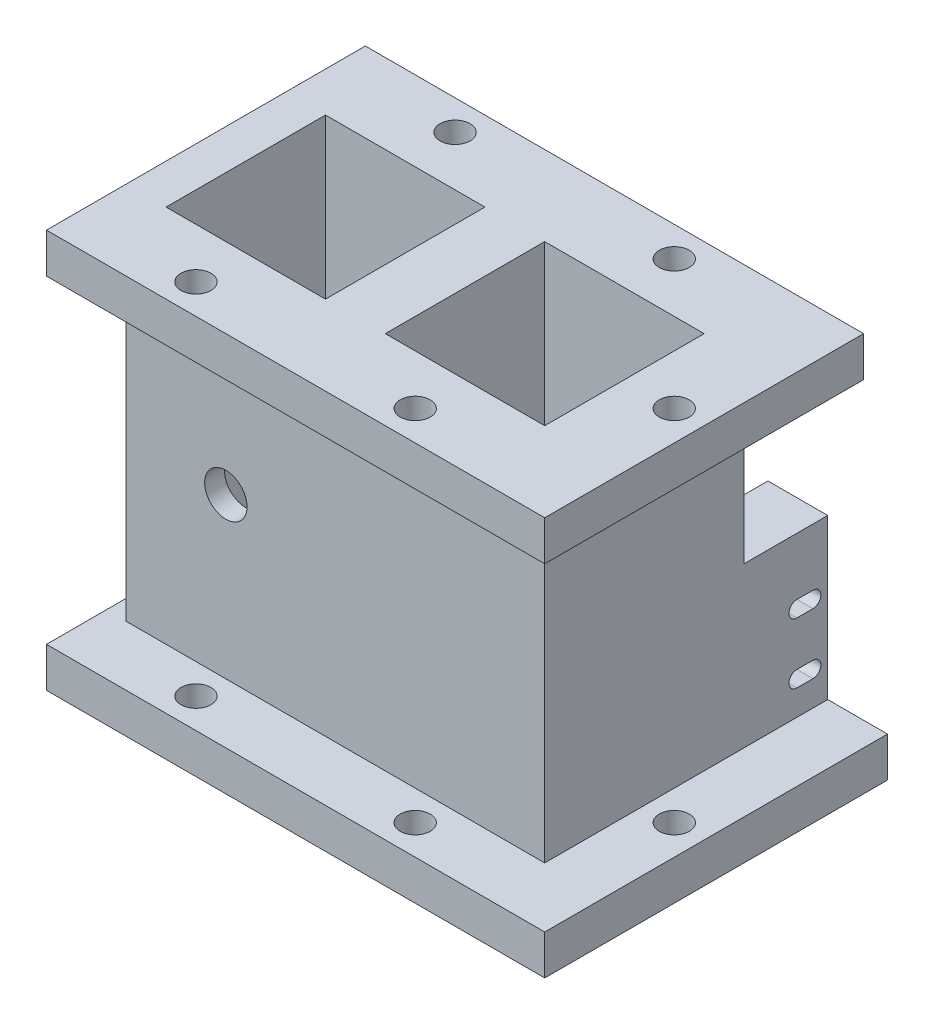
SolidWorks part; units mm, degrees
other "Markup1"
sketch "Sketch8" plane through (39.6875, 63.5, -25.4) normal (0.2237, 0.8347, -0.5032) x (-0.5017, -0.344, -0.7937)
other "Markup2"
sketch "Sketch16" plane through (-39.6875, 63.5, -25.4) normal (-0.7477, 0.2937, -0.5956) x (-0.6485, -0.1298, 0.7501)
other "Markup3"
sketch "Sketch18" plane through (40.5016, 64.1281, -25.9101) normal (0.6007, 0.1438, -0.7864) x (-0.7857, -0.0757, -0.614)
material "PPS"
ref_plane "Front Plane" through (0, 0, 0) normal (0, 0, 1) x (1, 0, 0)
ref_plane "Top Plane" through (0, 0, 0) normal (0, 1, 0) x (1, 0, 0)
ref_plane "Right Plane" through (0, 0, 0) normal (1, 0, 0) x (0, 0, -1)
sketch "Sketch2" plane through (0, 0, 0) normal (0, 1, 0) x (1, 0, 0)
  line L1 (-39.6875, -25.4) -> (39.6875, -25.4)
  line L2 (-39.6875, -25.4) -> (-39.6875, 25.4)
  line L3 (-39.6875, 25.4) -> (39.6875, 25.4)
  line L4 (39.6875, -25.4) -> (39.6875, 25.4)
  line L5 (-39.6875, -25.4) -> (39.6875, 25.4) construction
  line L6 (-39.6875, 25.4) -> (39.6875, -25.4) construction
  point P0 (0, 0)
  dimension "D1" = 50.8
  dimension "D2" = 79.375
extrude "Boss-Extrude1" add sketch "Sketch2" along normal blind 6.35 contours L4 L3 L2 L1
sketch "Sketch3" plane through (0, 6.35, 0) normal (0, 1, 0) x (1, 0, 0)
  line L0 (-39.6875, -25.4) -> (-39.6875, 25.4) construction
  line L1 (-33.3375, -12.7) -> (-7.9375, -12.7)
  line L2 (-33.3375, -12.7) -> (-33.3375, 12.7)
  line L3 (-33.3375, 12.7) -> (-7.9375, 12.7)
  line L4 (-7.9375, -12.7) -> (-7.9375, 12.7)
  line L5 (-33.3375, -12.7) -> (-7.9375, 12.7) construction
  line L6 (-33.3375, 12.7) -> (-7.9375, -12.7) construction
  line L7 (-39.6875, 0) -> (39.6875, 0) construction
  line L8 (1.5875, 12.7) -> (26.9875, 12.7)
  line L9 (1.5875, 12.7) -> (1.5875, -12.7)
  line L10 (1.5875, -12.7) -> (26.9875, -12.7)
  line L11 (26.9875, 12.7) -> (26.9875, -12.7)
  line L12 (1.5875, 12.7) -> (26.9875, -12.7) construction
  line L13 (1.5875, -12.7) -> (26.9875, 12.7) construction
  line L14 (39.6875, -25.4) -> (39.6875, 25.4) construction
  line L16 (-36.5125, -15.875) -> (30.1625, -15.875)
  line L17 (-36.5125, -15.875) -> (-36.5125, 15.875)
  line L18 (-36.5125, 15.875) -> (30.1625, 15.875)
  line L19 (30.1625, -15.875) -> (30.1625, 15.875)
  point P0 (-20.6375, 0)
  point P7 (14.2875, 0)
  dimension "D1" = 25.4
  dimension "D2" = 25.4
  dimension "D3" = 6.35
  dimension "D4" = 25.4
  dimension "D5" = 25.4
  dimension "D6" = 12.7
  dimension "D7" = 3.175
  dimension "D8" = 3.175
  dimension "D9" = 3.175
  dimension "D10" = 3.175
extrude "Boss-Extrude3" add sketch "Sketch3" along normal blind 50.8
sketch "Sketch4" plane through (0, 57.15, 0) normal (0, 1, 0) x (1, 0, 0)
  line L1 (-33.3375, 12.7) -> (-7.9375, 12.7)
  line L2 (-33.3375, 12.7) -> (-33.3375, -12.7)
  line L3 (-33.3375, -12.7) -> (-7.9375, -12.7)
  line L4 (-7.9375, 12.7) -> (-7.9375, -12.7)
  line L5 (1.5875, 12.7) -> (26.9875, 12.7)
  line L6 (1.5875, 12.7) -> (1.5875, -12.7)
  line L7 (1.5875, -12.7) -> (26.9875, -12.7)
  line L8 (26.9875, 12.7) -> (26.9875, -12.7)
ref_plane "Plane1" through (0, 31.75, 0) normal (0, 1, 0) x (1, 0, 0)
mirror "Mirror1" about plane through (0, 31.75, 0) normal (0, 1, 0) of "Boss-Extrude1"
extrude "Cut-Extrude4" cut sketch "Sketch4" against normal through all both and the other way through all
sketch "Sketch5" plane through (0, 0, 15.875) normal (0, 0, 1) x (1, 0, 0)
  line L0 (-36.5125, 31.75) -> (30.1625, 31.75) construction
  line L1 (-33.3375, 44.8114) -> (-7.9375, 44.8114) construction
  line L3 (-36.5125, 57.15) -> (-36.5125, 6.35) construction
  line L4 (30.1625, 57.15) -> (30.1625, 6.35) construction
  line L5 (-33.3375, 57.15) -> (-33.3375, 6.35) construction
  line L6 (-36.5125, 57.15) -> (30.1625, 57.15) construction
  line L7 (-36.5125, 6.35) -> (30.1625, 6.35) construction
  line L8 (-7.9375, 57.15) -> (-7.9375, 6.35) construction
  circle A0 centre (-20.6375, 31.75) radius 3.3782
  dimension "D1" = 6.7564
  dimension "D2" = 3.175
  dimension "D3" = 25.4
  dimension "D4" = 12.7
extrude "Cut-Extrude5" cut sketch "Sketch5" against normal through all
sketch "Sketch6" plane through (0, 6.35, 0) normal (0, 1, 0) x (1, 0, 0)
  line L0 (30.1625, 0) -> (39.6875, 0) construction
  line L1 (30.1625, -15.875) -> (30.1625, 15.875) construction
  line L2 (39.6875, -25.4) -> (39.6875, 25.4) construction
  circle A0 centre (34.925, 0) radius 2.3876
  dimension "D1" = 4.7752
ref_plane "Plane2" through (14.2875, 0, 0) normal (1, 0, 0) x (0, 0, -1)
ref_plane "Plane3" through (0, 0, 0) normal (0, 0, 1) x (1, 0, 0)
ref_axis "Axis1" through (14.2875, -3.175, 0) along (0, 1, 0)
extrude "Cut-Extrude6" cut sketch "Sketch6" against normal through all both and the other way through all
pattern_circular "CirPattern1" count 4 over 360 about axis through (14.2875, -3.175, 0) along (0, 1, 0) skipping 2 of "Cut-Extrude6"
sketch "Sketch7" plane through (0, 6.35, 0) normal (0, 1, 0) x (1, 0, 0)
  line L0 (-33.3375, -17.2263) -> (-33.3375, -22.8133) construction
  line L5 (-39.6875, -25.4) -> (-39.6875, 25.4) construction
  line L6 (-7.9375, -17.2263) -> (-7.9375, -22.8133) construction
  line L7 (-7.9375, -20.6375) -> (-33.3375, -20.6375) construction
  circle A1 centre (-20.6375, -20.6375) radius 2.3876
  dimension "D3" = 4.7752
  dimension "D1" = 6.35
  dimension "D2" = 25.4
extrude "Cut-Extrude7" cut sketch "Sketch7" against normal through all both and the other way through all
mirror "Mirror2" about plane through (0, 0, 0) normal (0, 0, 1) of "Cut-Extrude7"
sketch "Sketch9" plane through (0, 0, -15.875) normal (0, 0, -1) x (-1, 0, 0)
  line L0 (-30.1625, 57.15) -> (-30.1625, 6.35) construction
  line L1 (-23.8125, 6.35) -> (-1.5875, 6.35)
  line L2 (-23.8125, 6.35) -> (-23.8125, 31.75)
  line L3 (-23.8125, 31.75) -> (-1.5875, 31.75)
  line L4 (-1.5875, 6.35) -> (-1.5875, 31.75)
  line L6 (-30.1625, 6.35) -> (36.5125, 6.35) construction
  dimension "D1" = 6.35
  dimension "D2" = 28.575
  dimension "D3" = 0
  dimension "D4" = 25.4
extrude "Cut-Extrude8" cut sketch "Sketch9" against normal up to next
ref_plane "Plane5" through (30.1625, 0, 0) normal (1, 0, 0) x (0, 0, -1)
sketch "Sketch12" plane through (30.1625, 0, 0) normal (1, 0, 0) x (0, 0, -1)
  line L0 (25.4, 6.35) -> (25.4, 0) construction
  line L1 (12.7, 6.35) -> (25.4, 6.35)
  line L2 (12.7, 6.35) -> (12.7, 31.75)
  line L3 (12.7, 31.75) -> (25.4, 31.75)
  line L4 (25.4, 6.35) -> (25.4, 31.75)
  line L5 (12.7, 63.5) -> (12.7, 0) construction
  dimension "D1" = 25.4
extrude "Boss-Extrude5" add sketch "Sketch12" against normal blind 9.525
sketch "Sketch14" plane through (20.6375, 0, 0) normal (-1, 0, 0) x (0, 0, 1)
  line L0 (-12.7, 6.35) -> (-25.4, 6.35) construction
  line L1 (-25.4, 6.35) -> (-12.7, 6.35)
  line L2 (-25.4, 6.35) -> (-25.4, 26.162)
  line L3 (-25.4, 26.162) -> (-12.7, 26.162)
  line L4 (-12.7, 6.35) -> (-12.7, 26.162)
  dimension "D1" = 12.7
  dimension "D3" = 19.812
extrude "Cut-Extrude9" cut sketch "Sketch14" against normal blind 6.35
sketch "Sketch17" plane through (26.9875, 0, 0) normal (-1, 0, 0) x (0, 0, 1)
  line L8 (-12.7, 31.75) -> (-12.7, 26.162) construction
  circle A1 centre (-12.7, 26.1233) radius 5.588
  dimension "D2" = 11.176
  dimension "D1" = 0
extrude "Cut-Extrude11" cut sketch "Sketch17" along normal blind 6.985
ref_plane "Plane6" through (-50.8, 0, 0) normal (1, 0, 0) x (0, 0, -1)
sketch "Sketch19" plane through (0, 0, -25.4) normal (0, 0, -1) x (-1, 0, 0)
  line L0 (39.6875, 0) -> (-39.6875, 0) construction
  line L1 (-20.6375, 26.162) -> (-30.1625, 26.162)
  line L2 (-20.6375, 26.162) -> (-20.6375, 31.75)
  line L3 (-20.6375, 31.75) -> (-30.1625, 31.75)
  line L4 (-30.1625, 26.162) -> (-30.1625, 31.75)
  line L5 (-30.1625, 26.162) -> (-26.9875, 26.162)
  line L6 (-30.1625, 26.162) -> (-30.1625, 6.35)
  line L7 (-30.1625, 6.35) -> (-26.9875, 6.35)
  line L8 (-26.9875, 26.162) -> (-26.9875, 6.35)
  line L13 (-39.6875, 6.35) -> (-20.6375, 6.35)
  line L14 (-39.6875, 6.35) -> (-39.6875, 0)
  line L15 (-39.6875, 0) -> (-20.6375, 0)
  line L16 (-20.6375, 6.35) -> (-20.6375, 0)
  line M1 (-26.9875, 26.162) -> (-20.6375, 26.162)
  line M2 (-20.6375, 26.162) -> (-20.6375, 31.75)
  line M3 (-20.6375, 31.75) -> (-30.1625, 31.75)
  line M4 (-30.1625, 31.75) -> (-30.1625, 6.35)
  line M5 (-30.1625, 6.35) -> (-39.6875, 6.35)
  line M6 (-39.6875, 6.35) -> (-39.6875, 0)
  line M7 (-39.6875, 0) -> (39.6875, 0)
  line M8 (39.6875, 0) -> (39.6875, 6.35)
  line M9 (39.6875, 6.35) -> (-26.9875, 6.35)
  line M10 (-26.9875, 6.35) -> (-26.9875, 26.162)
extrude "Boss-Extrude6" add sketch "Sketch19" along normal blind 3.81 contours L1 M1 M2 M3 M4 | L7 L1 M4 M10 | L7 M5 M6 M7 M8 M9 region at (25.4, 28.956, -25.4) region at (28.575, 16.256, -25.4) region at (30.1625, 3.175, -25.4)
sketch "Sketch15" plane through (26.9875, 0, 0) normal (-1, 0, 0) x (0, 0, 1)
  line L0 (-12.6238, 20.788) -> (-12.6238, 10.696) construction
  line L1 (-29.21, 6.35) -> (-12.7, 6.35) construction
  line L2 (-15.875, 57.15) -> (-15.875, 31.75) construction
  line L3 (-26.8478, 21.336) -> (-24.3078, 21.336) construction
  line L4 (-26.8478, 22.606) -> (-24.3078, 22.606)
  line L5 (-26.8478, 20.066) -> (-24.3078, 20.066)
  line L6 (-26.8478, 11.684) -> (-24.3078, 11.684) construction
  line L7 (-26.8478, 12.954) -> (-24.3078, 12.954)
  line L8 (-26.8478, 10.414) -> (-24.3078, 10.414)
  circle A0 centre (-25.5778, 11.684) radius 1.27
  circle A1 centre (-25.5778, 21.336) radius 1.27
  arc A2 (-26.8478, 22.606) -> (-26.8478, 20.066) centre (-26.8478, 21.336) ccw
  arc A3 (-24.3078, 20.066) -> (-24.3078, 22.606) centre (-24.3078, 21.336) ccw
  arc A4 (-26.8478, 12.954) -> (-26.8478, 10.414) centre (-26.8478, 11.684) ccw
  arc A5 (-24.3078, 10.414) -> (-24.3078, 12.954) centre (-24.3078, 11.684) ccw
  point P13 (-25.5778, 21.336)
  point P20 (-25.5778, 11.684)
  dimension "D1" = 2.54
  dimension "D4" = 2.54
  dimension "D2" = 3.2512
  dimension "D3" = 5.334
  dimension "D5" = 12.954
  dimension "D6" = 9.652
  dimension "D7" = 2.54
  dimension "D8" = 2.54
  dimension "D9" = 2.54
  dimension "D10" = 2.54
extrude "Cut-Extrude10" cut sketch "Sketch15" against normal up to next contours L8 A5 L7 A0 | L7 A4 L8 A0 | A0 | L5 A3 L4 A1 | A1 | L4 A2 L5 A1 region at (26.9875, 21.336, -27.2103) region at (26.9875, 21.336, -23.9453) region at (26.9875, 21.336, -25.5778) region at (26.9875, 11.684, -27.2103) region at (26.9875, 11.684, -23.9453) region at (26.9875, 11.684, -25.5778)
scale "Scale1" scale about centroid uniform scaling yes scale factor 1.02
